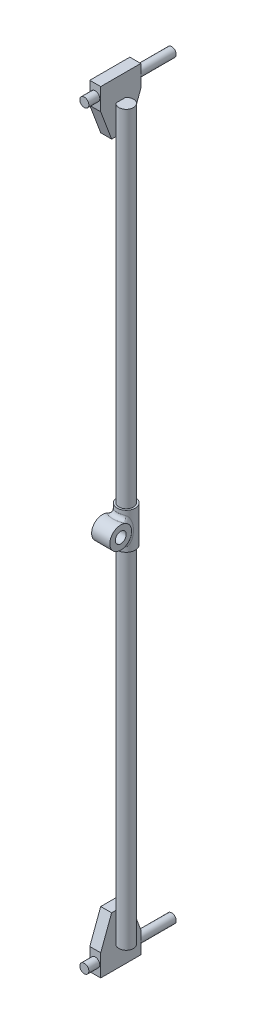
SolidWorks part; units mm, degrees
ref_plane "Front" through (0, 0, 0) normal (0, 0, 1) x (1, 0, 0)
ref_plane "Top" through (0, 0, 0) normal (0, 1, 0) x (1, 0, 0)
ref_plane "Right" through (0, 0, 0) normal (1, 0, 0) x (0, 0, -1)
sketch "草图1" plane through (0, 0, 0) normal (0, 1, 0) x (1, 0, 0)
  circle A0 centre (0, 0) radius 2
extrude "凸台-拉伸1" add sketch "草图1" along normal blind 200
ref_plane "基准面1" through (0, 100, 0) normal (0, 1, 0) x (1, 0, 0)
sketch "草图2" plane through (0, 100, 0) normal (0, 1, 0) x (1, 0, 0)
  circle A0 centre (0, 0) radius 2.5
extrude "凸台-拉伸2" add sketch "草图2" along normal blind 5 and the other way blind 5
ref_plane "基准面2" through (2.5, 0, 0) normal (1, 0, 0) x (0, 0, -1)
sketch "草图3" plane through (2.5, 0, 0) normal (1, 0, 0) x (0, 0, -1)
  line L0 (0, 95) -> (0, 105) construction
  line L1 (-2, 95) -> (2, 95) construction
  line L2 (2.5, 105) -> (-2.5, 105) construction
  line L3 (0, 100) -> (-4, 100) construction
  line L4 (50, 100) -> (-50, 100) construction
  circle A0 centre (-4, 100) radius 1.5
  circle A1 centre (-4, 100) radius 3
extrude "凸台-拉伸3" add sketch "草图3" against normal blind 5
fillet "圆角1" radius 1 1 edges at (-0.3468, 102.584, 2.4758)
ref_plane "基准面3" through (-1.5, 0, 0) normal (1, 0, 0) x (0, 0, -1)
sketch "草图5" plane through (-1.5, 0, 0) normal (1, 0, 0) x (0, 0, -1)
  line L0 (-4, 100) -> (-11.9368, 100) construction
  line L1 (50, 100) -> (-50, 100) construction
  line L2 (0, 200) -> (0, 192) construction
  line L3 (2, 200) -> (-2, 200) construction
  line L4 (0, 192) -> (-2.5, 192)
  line L5 (0, 200) -> (-5.5, 200) construction
  line L6 (-2.5, 192) -> (-5.5, 200)
  line L7 (-5.5, 200) -> (-5.5, 206)
  line L8 (-5.5, 206) -> (5.5, 206)
  line L9 (2.5, 192) -> (5.5, 200)
  line L10 (5.5, 200) -> (5.5, 206)
  line L11 (0, 192) -> (2.5, 192)
  line L12 (5.5, 0) -> (5.5, -6)
  line L13 (-5.5, -6) -> (5.5, -6)
  line L14 (-5.5, 0) -> (-5.5, -6)
  line L15 (-2.5, 8) -> (-5.5, 0)
  line L16 (0, 8) -> (-2.5, 8)
  line L17 (0, 8) -> (2.5, 8)
  line L18 (2.5, 8) -> (5.5, 0)
  point P17 (0, 206)
extrude "凸台-拉伸4" add sketch "草图5" against normal blind 3 separate body
ref_plane "基准面4" through (0, 0, 8.5) normal (0, 0, 1) x (1, 0, 0)
sketch "草图6" plane through (0, 0, 8.5) normal (0, 0, 1) x (1, 0, 0)
  line L0 (-4.5, 206) -> (-1.5, 206) construction
  line L1 (-1.5, 206) -> (-1.5, 200) construction
  line L2 (-36.3156, 100) -> (16.3382, 100) construction
  line L3 (50, 100) -> (-50, 100) construction
  circle A0 centre (-3.0049, 203) radius 1.25
  circle A1 centre (-3.0049, -3) radius 1.25
  dimension "D3" = 2.5
  dimension "D1" = 3
  dimension "D2" = 1.5049
extrude "凸台-拉伸5" add sketch "草图6" against normal blind 24
